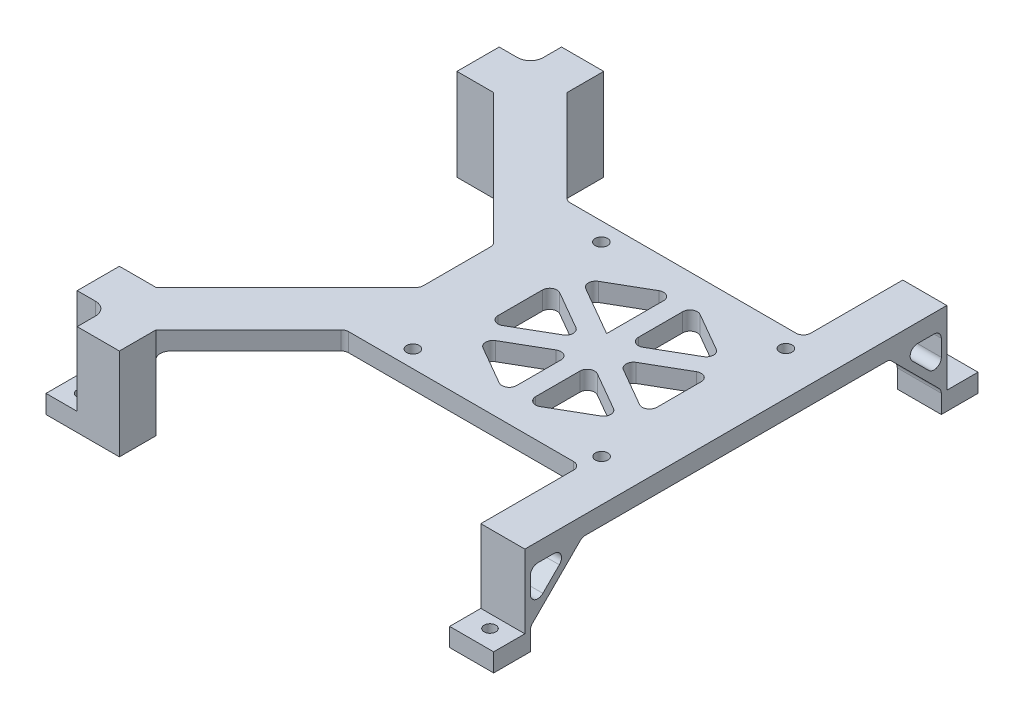
SolidWorks part; units mm, degrees
ref_plane "Plan de face" through (0, 0, 0) normal (0, 0, 1) x (1, 0, 0)
ref_plane "Plan de dessus" through (0, 0, 0) normal (0, 1, 0) x (1, 0, 0)
ref_plane "Plan de droite" through (0, 0, 0) normal (1, 0, 0) x (0, 0, -1)
sketch "Esquisse1" plane through (0, 0, 0) normal (0, 1, 0) x (1, 0, 0)
  line L0 (-55, -46) -> (-65, -46)
  line L1 (-65, -46) -> (-65, -66)
  line L2 (-65, -66) -> (-45, -66)
  line L3 (-45, -66) -> (-45, -56)
  line L5 (-55, -46) -> (-55, -56)
  line L14 (-55, -56) -> (-45, -56)
  line L25 (0, 0) -> (-166.0367, 0) construction
  line L30 (45, -56) -> (57, -56)
  line L31 (45, -56) -> (45, -66)
  line L32 (45, -66) -> (57, -66)
  line L33 (57, -56) -> (57, -66)
  line L34 (-65, 56) -> (-55, 66) construction
  line L35 (45, 66) -> (57, 56) construction
  line L36 (-55, 56) -> (-65, 66) construction
  line L37 (-55, -56) -> (-65, -66) construction
  line L38 (45, -66) -> (57, -56) construction
  line L39 (-65, -56) -> (-55, -66) construction
  line L42 (57, 56) -> (57, 66)
  line L43 (45, 66) -> (57, 66)
  line L44 (45, 56) -> (45, 66)
  line L45 (45, 56) -> (57, 56)
  line L46 (-55, 56) -> (-45, 56)
  line L47 (-55, 46) -> (-55, 56)
  line L48 (-45, 66) -> (-45, 56)
  line L49 (-65, 66) -> (-45, 66)
  line L50 (-65, 46) -> (-65, 66)
  line L51 (-55, 46) -> (-65, 46)
  point P21 (-60, -61)
  point P32 (51, -61)
  point P39 (51, 61)
  point P40 (-60, 61)
  dimension "D1" = 10
  dimension "D2" = 90
  dimension "D3" = 10
  dimension "D4" = 10
  dimension "D10" = 12
  dimension "D12" = 45
  dimension "D13" = 45
  dimension "D15" = 20
  dimension "D16" = 20
  dimension "D19" = 90
  dimension "D20" = 90
  dimension "D24" = 90
  dimension "D25" = 90
  dimension "D26" = 56
  dimension "D28" = 66
extrude "Boss.-Extru.1" add sketch "Esquisse1" along normal blind 25
ref_plane "Plan1" through (0, 25, 0) normal (0, 1, 0) x (1, 0, 0)
sketch "Esquisse28" plane through (0, 25, 0) normal (0, 1, 0) x (1, 0, 0)
  line L0 (57, -56) -> (45, -56) construction
  line L1 (45, -56) -> (45, -30.192) construction
  line L3 (45, -30.192) -> (-19.192, -30.192) construction
  line L4 (-19.192, -30.192) -> (-45, -56) construction
  line L5 (-45, -56) -> (-55, -56) construction
  line L6 (-55, -56) -> (-55, -46) construction
  line L7 (-55, -46) -> (-19, -10) construction
  line L8 (-19, -10) -> (-19, 10) construction
  line L9 (-19, 10) -> (-55, 46) construction
  line L10 (-55, 46) -> (-55, 56) construction
  line L11 (-55, 56) -> (-45, 56) construction
  line L12 (-45, 56) -> (-19.4093, 30.4093) construction
  line L13 (-19.4093, 30.4093) -> (45, 30.4093) construction
  line L15 (45, 30.4093) -> (45, 56) construction
  line L19 (0, 0) -> (-166.0367, 0) construction
  line L20 (45, 56) -> (57, 56) construction
  line L21 (57, 56) -> (57, -56) construction
  circle A0 centre (45.237, 25.4093) radius 1.705 construction
  circle A1 centre (45.6027, -25.192) radius 1.705 construction
  circle A2 centre (-5.0396, 25.4093) radius 1.705 construction
  circle A3 centre (-5.4704, -25.5275) radius 1.705 construction
  dimension "D1" = 135
  dimension "D2" = 90
  dimension "D5" = 5
  dimension "D6" = 135
  dimension "D7" = 5
  dimension "D8" = 10
sketch "Esquisse2" plane through (0, 25, 0) normal (0, -1, 0) x (1, 0, 0)
  circle A0 centre (-5.4704, 25.5275) radius 1.705 construction
  circle A1 centre (45.237, -25.4093) radius 1.705 construction
  circle A2 centre (-5.0396, -25.4093) radius 1.705 construction
  circle A3 centre (45.6027, 25.192) radius 1.705 construction
sketch "Esquisse3" plane through (0, 25, 0) normal (0, 1, 0) x (1, 0, 0)
  line L80 (-19.192, -30.192) -> (-45, -56)
  line L94 (-45, -56) -> (-55, -56)
  line L96 (-55, -56) -> (-55, -46)
  line L99 (-55, -46) -> (-19, -10)
  line L102 (-19, -10) -> (-19, 10)
  line L109 (-19, 10) -> (-55, 46)
  line L110 (-55, 46) -> (-55, 56)
  line L111 (-55, 56) -> (-45, 56)
  line L112 (-45, 56) -> (-19.4093, 30.4093)
  line L113 (-19.4093, 30.4093) -> (45, 30.4093)
  line L114 (45, 30.4093) -> (45, 56)
  line L115 (45, 56) -> (57, 56)
  line L116 (57, 56) -> (57, -56)
  line L117 (57, -56) -> (45, -56)
  line L118 (45, -56) -> (45, -30.192)
  line L119 (45, -30.192) -> (-19.192, -30.192)
extrude "Boss.-Extru.2" add sketch "Esquisse3" against normal blind 5
sketch "Esquisse5" plane through (0, 25, 0) normal (0, -1, 0) x (1, 0, 0)
  line L1 (-65, 66) -> (-56.5, 66)
  line L2 (-65, 66) -> (-45, 66) construction
  line L3 (-56.5, 66) -> (-56.5, 61)
  line L4 (-65, 66) -> (-65, 57.5)
  line L5 (-65, 46) -> (-65, 66) construction
  line L6 (-65, 57.5) -> (-60, 57.5)
  line L7 (-55, 56) -> (-65, 66) construction
  arc A4 (-56.5, 61) -> (-60, 57.5) centre (-60, 61) cw
  dimension "D1" = 5
  dimension "D2" = 5
  dimension "D3" = 8.5
  dimension "D4" = 8.5
  dimension "D5" = 3.5
extrude "Enlèv. mat.-Extru.1" cut sketch "Esquisse5" along normal blind 20
sketch "Esquisse6" plane through (0, 25, 0) normal (0, -1, 0) x (1, 0, 0)
  line L4 (-65, -66) -> (-56.5, -66)
  line L5 (-65, -66) -> (-65, -57.5)
  line L6 (-56.5, -66) -> (-56.5, -61)
  line L7 (-65, -57.5) -> (-60, -57.5)
  line L8 (-55, -56) -> (-65, -66) construction
  arc A3 (-60, -57.5) -> (-56.5, -61) centre (-60, -61) cw
  dimension "D1" = 8.5
  dimension "D5" = 3.5
  dimension "D2" = 0
  dimension "D3" = 5
  dimension "D4" = 5
  dimension "D6" = 8.5
sketch "Esquisse7" plane through (0, 25, 0) normal (0, -1, 0) x (1, 0, 0)
  line L0 (57, -66) -> (45, -66)
  line L7 (45, -66) -> (57, -66) construction
  line L9 (57, -66) -> (57, -57.5)
  line L10 (57, -56) -> (57, -66) construction
  line L11 (57, -57.5) -> (45, -57.5)
  line L13 (45, -56) -> (45, -66) construction
  line L14 (45, -66) -> (45, -57.5)
  dimension "D2" = 8.5
sketch "Esquisse8" plane through (0, 25, 0) normal (0, -1, 0) x (1, 0, 0)
  line L1 (57, 56) -> (57, 66) construction
  line L2 (57, 57.5) -> (57, 66)
  line L4 (57, 57.5) -> (45, 57.5)
  line L7 (45, 56) -> (45, 66) construction
  line L8 (45, 57.5) -> (45, 66)
  line L9 (45, 66) -> (57, 66)
  dimension "D1" = 12
  dimension "D4" = 8.5
  dimension "D7" = 0
extrude "Enlèv. mat.-Extru.6" cut sketch "Esquisse6" along normal blind 20
extrude "Enlèv. mat.-Extru.7" cut sketch "Esquisse7" along normal blind 20
extrude "Enlèv. mat.-Extru.8" cut sketch "Esquisse8" along normal blind 20
hole_wizard "Dégagement M31" positions "Esquisse11" profile "Esquisse12" hole size "M3" standard "Ansi Metric" end condition through all
sketch "Esquisse11" plane through (0, 20, 0) normal (0, -1, 0) x (-1, 0, 0)
  point P0 (5.0396, 25.4093)
  point P3 (-45.237, 25.4093)
  point P6 (-45.6027, -25.192)
  point P9 (5.4704, -25.5275)
sketch "Esquisse12" plane through (-5.0396, 20, -25.4093) normal (1, 0, 0) x (0, 0, -1)
  line L0 (0, 0) -> (0, 5)
  line L1 (0, 5) -> (1.7, 5)
  line L2 (1.7, 5) -> (1.7, 0)
  line L5 (1.7, 0) -> (0, 0)
  line L11 (0, -6.35) -> (0, 107.95) construction
  dimension "Diamètre du perçage jusqu'au prochain" = 3.4
  dimension "Profondeur du perçage jusqu'au prochain" = 5
hole_wizard "Dégagement M33" positions "Esquisse32" profile "Esquisse33" hole size "M3" standard "Ansi Metric" end condition through all
sketch "Esquisse32" plane through (0, 5, 0) normal (0, 1, 0) x (1, 0, 0)
  point P0 (-60, 61)
  point P3 (51, 61)
  point P6 (51, -61)
  point P9 (-60, -61)
sketch "Esquisse33" plane through (-60, 5, -61) normal (1, 0, 0) x (0, 0, 1)
  line L0 (0, 0) -> (0, 5)
  line L1 (0, 5) -> (1.6, 5)
  line L2 (1.6, 5) -> (1.6, 0)
  line L5 (1.6, 0) -> (0, 0)
  line L11 (0, -6.35) -> (0, 107.95) construction
  dimension "Diamètre du perçage jusqu'au prochain" = 3.2
  dimension "Profondeur du perçage jusqu'au prochain" = 5
sketch "Esquisse26" plane through (0, 20, 0) normal (0, -1, 0) x (-1, 0, 0)
  line L1 (-41.5339, 12.5) -> (-41.5339, -12.5)
  line L2 (-41.5339, -12.5) -> (-19.8833, -25)
  line L3 (-19.8833, -25) -> (1.7673, -12.5)
  line L4 (1.7673, -12.5) -> (1.7673, 12.5)
  line L5 (1.7673, 12.5) -> (-19.8833, 25)
  line L6 (-19.8833, 25) -> (-41.5339, 12.5)
  line L8 (5.0396, 25.4093) -> (-45.6027, -25.192) construction
  line L9 (5.4704, -25.5275) -> (-45.237, 25.4093) construction
  circle A1 centre (-19.8833, 0) radius 21.6506 construction
  point P2 (-19.8833, -0.0591)
  dimension "D1" = 19.8833
  dimension "D2" = 25
  dimension "D3" = 0
extrude "Enlèv. mat.-Extru.5" cut sketch "Esquisse26" against normal up to next
sketch "Esquisse27" plane through (0, 20, 0) normal (0, -1, 0) x (-1, 0, 0)
  line L0 (1.7673, 12.5) -> (-19.8833, 25) construction
  line L1 (-19.8833, -25) -> (1.7673, -12.5) construction
  line L3 (-19.8833, 25) -> (-19.8833, -25) construction
  line L5 (-22.4814, -23.5) -> (-19.8833, -25)
  line L7 (-22.4814, -23.5) -> (-22.4814, -4.5)
  line L8 (-22.4814, 23.5) -> (-22.4814, 4.5)
  line L9 (-41.5339, 9.5) -> (-25.0794, 0)
  line L11 (-38.9359, 14) -> (-22.4814, 4.5)
  line L12 (-22.4814, -4.5) -> (-38.9359, -14)
  line L14 (-41.5339, -9.5) -> (-25.0794, 0)
  line L16 (-19.8833, 25) -> (-22.4814, 23.5)
  line L19 (-38.9359, 14) -> (-41.5339, 12.5)
  line L26 (1.7673, -12.5) -> (-0.8307, -14)
  line L27 (1.7673, -9.5) -> (1.7673, -12.5)
  line L30 (1.7673, 12.5) -> (1.7673, 9.5)
  line L31 (-0.8307, 14) -> (1.7673, 12.5)
  line L32 (-19.8833, 25) -> (-17.2852, 23.5)
  line L33 (1.7673, -9.5) -> (-14.6871, 0)
  line L34 (-17.2852, -4.5) -> (-0.8307, -14)
  line L35 (-0.8307, 14) -> (-17.2852, 4.5)
  line L36 (1.7673, 9.5) -> (-14.6871, 0)
  line L37 (-17.2852, 23.5) -> (-17.2852, 4.5)
  line L38 (-17.2852, -23.5) -> (-17.2852, -4.5)
  line L39 (-17.2852, -23.5) -> (-19.8833, -25)
  line L40 (-19.8833, 25) -> (-41.5339, 12.5) construction
  line L41 (-41.5339, 12.5) -> (-41.5339, -12.5) construction
  line L42 (-41.5339, -12.5) -> (-19.8833, -25) construction
  line L43 (-41.5339, 12.5) -> (-41.5339, 9.5)
  line L44 (-41.5339, -9.5) -> (-41.5339, -12.5)
  line L45 (-41.5339, -12.5) -> (-38.9359, -14)
  dimension "D1" = 60
  dimension "D2" = 3
  dimension "D3" = 60
  dimension "D4" = 3
  dimension "D5" = 3
  dimension "D6" = 3
  dimension "D7" = 3
  dimension "D8" = 60
  dimension "D9" = 3
extrude "Boss.-Extru.5" add sketch "Esquisse27" against normal blind 5
fillet "Congé6" radius 2 27 edges at (17.2852, 22.5, 4.5) (14.6871, 22.5, 0) (0.8307, 22.5, -14) (22.4814, 22.5, -23.5) (38.9359, 22.5, -14) (41.5339, 22.5, -9.5) (41.5339, 22.5, 9.5) (17.2852, 22.5, 23.5) (0.8307, 22.5, 14) (38.9359, 22.5, 14) (22.4814, 22.5, 23.5) (-1.7673, 22.5, -9.5) (45, 22.5, 30.192) (-19.192, 22.5, 30.192) (51, 20, 56) (-50, 20, 56) (-55, 20, 51) (-19, 22.5, -10) (-19, 22.5, 10) (45, 22.5, -30.4093) (-19.4093, 22.5, -30.4093) (25.0794, 22.5, 0) (22.4814, 22.5, -4.5) (-1.7673, 22.5, 9.5) (22.4814, 22.5, 4.5) (17.2852, 22.5, -23.5) (51, 20, -56)
sketch "Esquisse35" plane through (57, 0, 0) normal (1, 0, 0) x (0, 0, -1)
  line L0 (-56, 5.8579) -> (-41.8579, 20)
  line L1 (-56, 18) -> (-56, 0) construction
  line L2 (-54, 20) -> (54, 20) construction
  line L3 (-41.8579, 20) -> (-44.6863, 20)
  line L4 (-44.6863, 20) -> (-56, 8.6863)
  line L5 (-56, 8.6863) -> (-56, 5.8579)
  line L6 (-56, 18) -> (-56, 0) construction
  line L7 (-54, 20) -> (-44, 20) construction
  line L8 (0, 0) -> (0, 38.4131) construction
  line L9 (56, 8.6863) -> (56, 5.8579)
  line L10 (44.6863, 20) -> (56, 8.6863)
  line L11 (41.8579, 20) -> (44.6863, 20)
  line L12 (56, 5.8579) -> (41.8579, 20)
  dimension "D1" = 135
  dimension "D2" = 45
  dimension "D3" = 20
  dimension "D4" = 2
extrude "Boss.-Extru.6" add sketch "Esquisse35" against normal up to surface (12 mm away) up to face at (45, 13.1571, -53.137)
fillet "Congé7" radius 2 8 edges at (51, 20, 44.6863) (51, 20, -44.6863) (51, 8.6863, -56) (51, 20, -41.8579) (51, 5.8579, -56) (51, 20, 41.8579) (51, 5.8579, 56) (51, 8.6863, 56)
